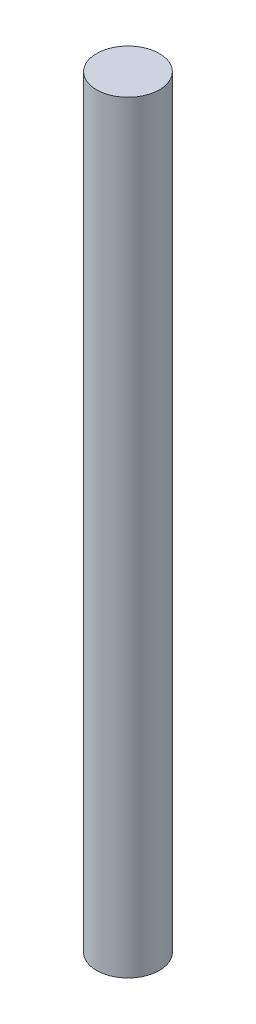
SolidWorks part; units mm, degrees
ref_plane "Front Plane" through (0, 0, 0) normal (0, 0, 1) x (1, 0, 0)
ref_plane "Top Plane" through (0, 0, 0) normal (0, 1, 0) x (1, 0, 0)
ref_plane "Right Plane" through (0, 0, 0) normal (1, 0, 0) x (0, 0, -1)
sketch "Elevation Bar" plane through (0, 0, 0) normal (0, 1, 0) x (1, 0, 0)
  circle A0 centre (0, 0) radius 30.226
  dimension "D1" = 60.452
extrude "Elevation Bar Part" add sketch "Elevation Bar" along normal blind 734.06
sketch "Sketch2" plane through (0, 0, 0) normal (0, 0, 1) x (1, 0, 0)
  line L0 (0, 0) -> (172.1794, 0) construction
  line L1 (-30.226, 0) -> (-30.226, 734.06) construction
  line L2 (-30.226, 734.06) -> (30.226, 734.06) construction
  line L3 (30.226, 734.06) -> (30.226, 0) construction
  line L4 (30.226, 0) -> (30.226, 734.06) construction
  line L5 (636.651, 40.7185) -> (27.051, 40.7185) construction
  line L6 (636.651, 53.4185) -> (27.051, 53.4185)
  line L7 (636.651, 53.4185) -> (636.651, 28.0185)
  line L8 (636.651, 28.0185) -> (27.051, 28.0185)
  line L9 (27.051, 53.4185) -> (27.051, 28.0185)
  line L10 (-30.226, 93.98) -> (30.226, 93.98) construction
  line L11 (33.2486, 0) -> (-33.2486, 0) construction
  line L12 (30.226, 185.42) -> (-30.226, 185.42) construction
  line L13 (30.226, 276.86) -> (-30.226, 276.86) construction
  line L14 (30.226, 368.3) -> (-30.226, 368.3) construction
  line L15 (30.226, 459.74) -> (-30.226, 459.74) construction
  line L16 (30.226, 551.18) -> (-30.226, 551.18) construction
  line L17 (30.226, 642.62) -> (-30.226, 642.62) construction
  line L18 (30.226, 73.152) -> (750.8896, 73.152) construction
  circle A0 centre (576.5632, 40.7185) radius 41.275 construction
  circle A1 centre (87.1388, 40.7185) radius 41.275 construction
  circle A2 centre (331.851, 40.7185) radius 41.275 construction
  point P24 (331.851, 40.7185)
  dimension "D2" = 82.55
  dimension "D1" = 609.6
  dimension "D3" = 25.4
  dimension "D4" = 244.7122
  dimension "D5" = 244.7122
  dimension "D6" = 93.98
  dimension "D7" = 185.42
  dimension "D8" = 276.86
  dimension "D9" = 368.3
  dimension "D10" = 459.74
  dimension "D11" = 551.18
  dimension "D12" = 642.62
  dimension "D13" = 73.152
sketch "Sketch4" plane through (0, 0, 0) normal (0, 0, 1) x (1, 0, 0)
  line L0 (-30.226, 182.88) -> (-30.226, 101.727) construction
  line L1 (52.451, 101.727) -> (27.051, 101.727) construction
  line L2 (-30.226, 0) -> (-30.226, 734.06) construction
  line L3 (30.226, 734.06) -> (30.226, 0) construction
  line L4 (-30.226, 182.88) -> (30.226, 101.727) construction
  line L5 (30.226, 101.727) -> (-30.226, 101.727) construction
  line L6 (27.051, 101.727) -> (-30.226, 182.88) construction
  line L7 (27.051, 101.727) -> (27.051, 40.7185) construction
  line L8 (30.226, 226.8605) -> (203.668, 53.4185) construction
  line L10 (30.226, 73.152) -> (750.8896, 73.152) construction
  line L11 (636.651, 53.4185) -> (27.051, 53.4185) construction
  circle A0 centre (52.451, 101.727) radius 20.6375
  circle A1 centre (52.451, 101.727) radius 25.4
  circle A2 centre (52.451, 101.727) radius 22.225 construction
  circle A3 centre (-55.626, 182.88) radius 25.4
  circle A4 centre (81.026, 104.2185) radius 50.8 construction
  point P22 (52.451, 102.4071)
  dimension "D1" = 50.8
  dimension "D2" = 41.275
  dimension "D3" = 1.5875
  dimension "D4" = 3.175
  dimension "D5" = 182.88
  dimension "D8" = 101.6
  dimension "D6" = 50.8
  dimension "D7" = 81.153
  dimension "D9" = 45
  dimension "D10" = 54.786
  dimension "D11" = 53.317
  dimension "D12" = 48.3085
ref_plane "Plane1" through (0, 53.4185, 0) normal (0, 1, 0) x (1, 0, 0)
equation "\"D5@Sketch2\"=\"D4@Sketch2\""
